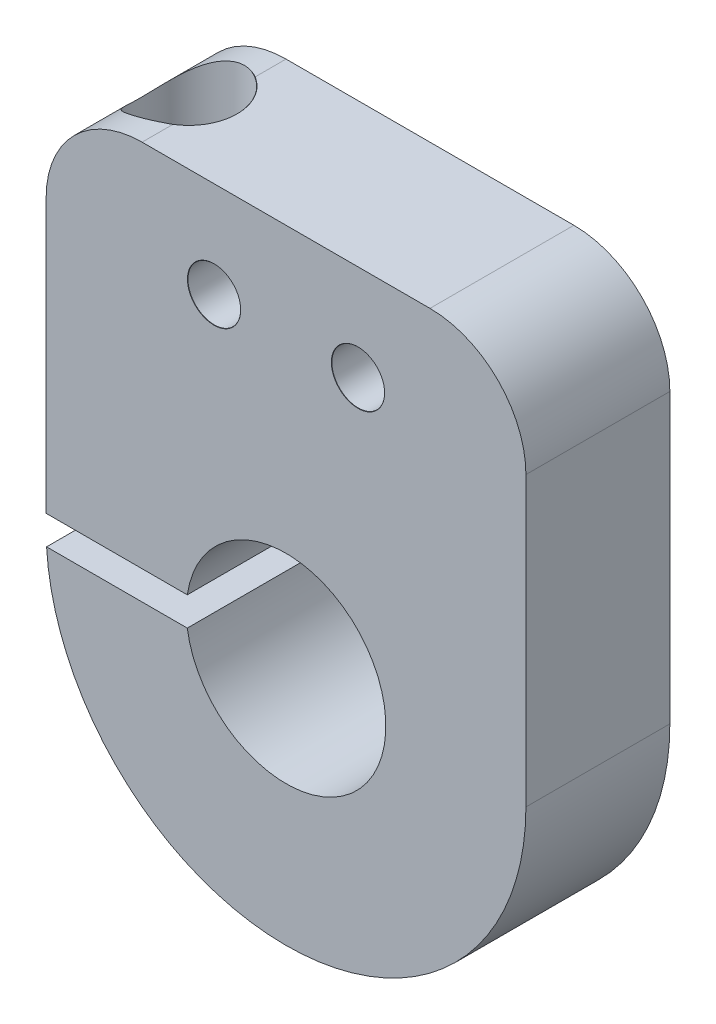
SolidWorks part; units mm, degrees
ref_plane "Front Plane" through (0, 0, 0) normal (0, 0, 1) x (1, 0, 0)
ref_plane "Top Plane" through (0, 0, 0) normal (0, 1, 0) x (1, 0, 0)
ref_plane "Right Plane" through (0, 0, 0) normal (1, 0, 0) x (0, 0, -1)
sketch "Sketch2" plane through (0, 0, 0) normal (0, 0, 1) x (1, 0, 0)
  line L0 (-25, 0) -> (-25, 40)
  line L1 (-25, 40) -> (25, 40)
  line L2 (25, 40) -> (25, 0)
  line L3 (25, 0) -> (-25, 0)
  circle A0 centre (0, 0) radius 25
  circle A1 centre (0, 0) radius 10.4
  dimension "D1" = 20.8
  dimension "D2" = 50
  dimension "D3" = 40
extrude "Boss-Extrude1" add sketch "Sketch2" along normal blind 15 contours A0 L2 L1 L0 | A1 L3 A0 | A1 L3 A0 region at (0, 11.9071, 0) region at (0, 29.053, 0) region at (0, -11.9071, 0)
sketch "Sketch3" plane through (0, 0, 15) normal (0, 0, 1) x (1, 0, 0)
  line L0 (-25, 0) -> (-25, 40) construction
  line L1 (-25, 1.5) -> (-10.2913, 1.5)
  line L2 (-25, 1.5) -> (-25, -1.5)
  line L3 (-25, -1.5) -> (-10.2913, -1.5)
  line L4 (-10.2913, 1.5) -> (-10.2913, -1.5)
  circle A2 centre (0, 0) radius 10.4 construction
  point P4 (-10.2913, 0)
  dimension "D1" = 3
extrude "Cut-Extrude1" cut sketch "Sketch3" against normal through all
sketch "Sketch11" plane through (0, 40, 0) normal (0, 1, 0) x (1, 0, 0)
  line L1 (-24.955, -15) -> (-10.2913, -15) construction
  line L2 (-25, -15) -> (-25, 0) construction
  point P0 (-17.6231, -7.5)
  point P10 (-17.6231, -15)
  point P13 (-25, -7.5)
hole_wizard "CBORE for M5 SHCS3" positions "Sketch11" profile "Sketch10" counterbore size "M5" standard "ANSI Metric" end condition through all
sketch "Sketch10" plane through (-17.6231, 40, 7.5) normal (1, 0, 0) x (0, 0, 1)
  line L0 (0, 0) -> (0, 65)
  line L1 (0, 65) -> (2.75, 65)
  line L3 (2.75, 65) -> (2.75, 10)
  line L4 (5, 10) -> (2.75, 10)
  line L5 (5, 10) -> (5, 0.025)
  line L6 (5, 0.025) -> (5.025, 0)
  line L7 (5.025, 0) -> (0, 0)
  line L8 (-5, 0.025) -> (-5.025, 0) construction
  line L11 (0, -6.35) -> (0, 107.95) construction
  dimension "Thru Hole Dia." = 5.5
  dimension "Thru Hole Depth" = 65
  dimension "C'Bore Dia." = 10
  dimension "C'Bore Depth" = 10
  dimension "Near C'Sink Dia." = 10.05
  dimension "Near C'Sink Angle" = 90
sketch "Sketch17" plane through (0, 0, 15) normal (0, 0, 1) x (1, 0, 0)
  line L0 (-7.5, 30) -> (7.5, 30) construction
  line L2 (-25, 40) -> (25, 40) construction
  point P0 (-7.5, 30)
  point P2 (7.5, 30)
  point P9 (0, 30)
  dimension "D1" = 15
  dimension "D2" = 10
hole_wizard "M5 Clearance Hole1" positions "Sketch17" profile "Sketch15" hole size "M5" standard "ANSI Metric" end condition through all
sketch "Sketch15" plane through (-7.5, 30, 15) normal (1, 0, 0) x (0, -1, 0)
  line L0 (0, 0) -> (0, 15)
  line L1 (0, 15) -> (2.75, 15)
  line L2 (2.75, 15) -> (2.75, 0.025)
  line L3 (2.75, 0.025) -> (2.775, 0)
  line L5 (2.775, 0) -> (0, 0)
  line L6 (-2.75, 0.025) -> (-2.775, 0) construction
  line L11 (0, -6.35) -> (0, 107.95) construction
  dimension "Thru Hole Dia." = 5.5
  dimension "Thru Hole Depth" = 15
  dimension "Near C'Sink Dia." = 5.55
  dimension "Near C'Sink Angle" = 90
fillet "Fillet1" radius 10 2 edges at (-25, 40, 7.5) (25, 40, 7.5)
ref_plane "Plane1" through (0, -11.5, 0) normal (0, 1, 0) x (1, 0, 0)
sketch "Sketch18" plane through (0, -11.5, 0) normal (0, 1, 0) x (1, 0, 0)
  line L0 (-19.9902, -3.4) -> (-15.256, -3.4)
  line L1 (-15.256, -3.4) -> (-12.8888, -7.5)
  line L2 (-12.8888, -7.5) -> (-15.256, -11.6)
  line L3 (-15.256, -11.6) -> (-19.9902, -11.6)
  line L4 (-19.9902, -11.6) -> (-22.3574, -7.5)
  line L5 (-22.3574, -7.5) -> (-19.9902, -3.4)
  line L6 (-21.1738, -9.55) -> (-14.0724, -5.45) construction
  line L8 (-25, -15) -> (-25, 0) construction
  line L10 (-24.955, -15) -> (-10.2913, -15) construction
  point P8 (-14.0724, -5.45)
  point P12 (-25, -7.5)
  point P13 (-17.6231, -7.5)
  point P19 (-17.6231, -15)
  dimension "D1" = 120
  dimension "D2" = 120
  dimension "D3" = 8.2
extrude "Cut-Extrude2" cut sketch "Sketch18" against normal through all
